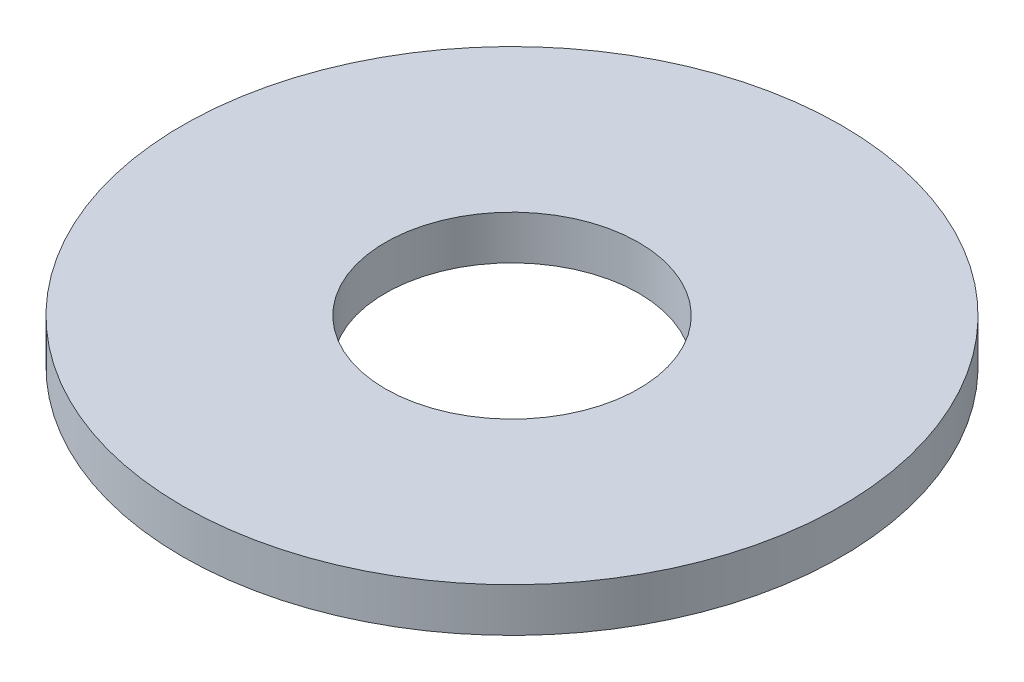
SolidWorks part; units mm, degrees
ref_plane "Front Plane" through (0, 0, 0) normal (0, 0, 1) x (1, 0, 0)
ref_plane "Top Plane" through (0, 0, 0) normal (0, 1, 0) x (1, 0, 0)
ref_plane "Right Plane" through (0, 0, 0) normal (1, 0, 0) x (0, 0, -1)
sketch "Sketch1" plane through (0, 0, 0) normal (0, 1, 0) x (1, 0, 0)
  circle A0 centre (0, 0) radius 97.5
  dimension "FLANGE_OD" = 195
extrude "Boss-Extrude1" add sketch "Sketch1" along normal blind 13
sketch "Sketch2" plane through (0, 0, 0) normal (0, 1, 0) x (1, 0, 0)
  circle A0 centre (0, 0) radius 37.5
  dimension "BORE_D" = 75
extrude "Cut-Extrude1" cut sketch "Sketch2" along normal through all
sketch "Sketch3" plane through (0, 13, 0) normal (0, 1, 0) x (1, 0, 0)
  circle A0 centre (0, 0) radius 28.5214 construction
  circle A1 centre (-28.5214, 0) radius 2.674
  dimension "BOLT_D" = 5.3481
  dimension "BOLT_PCD" = 57.0428
extrude "Cut-Extrude2" cut sketch "Sketch3" against normal blind 10.4031 rebuild error yes
pattern_circular "CirPattern1" count 5 over 360 rebuild error yes
